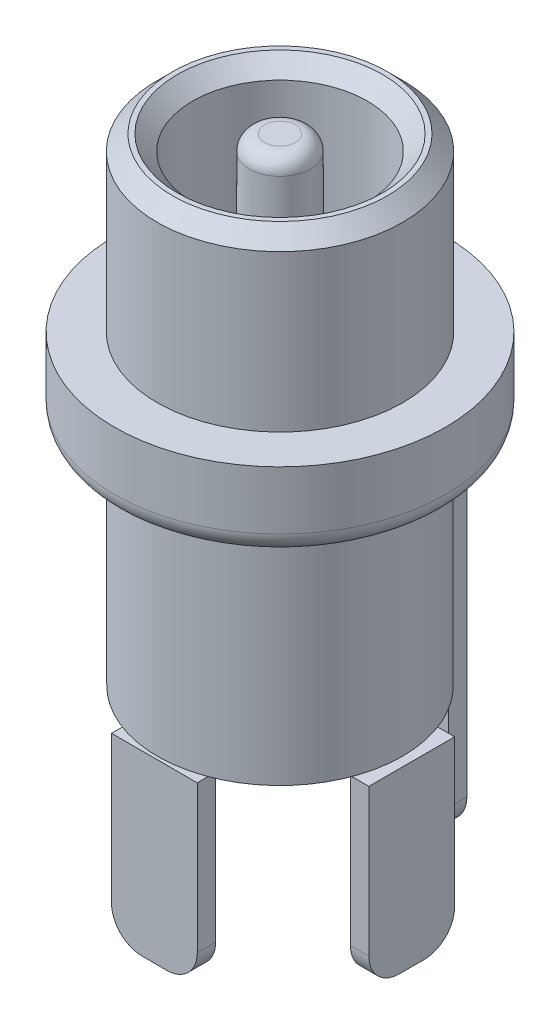
SolidWorks part; units mm, degrees
ref_plane "Front Plane" through (0, 0, 0) normal (0, 0, 1) x (1, 0, 0)
ref_plane "Top Plane" through (0, 0, 0) normal (0, 1, 0) x (1, 0, 0)
ref_plane "Right Plane" through (0, 0, 0) normal (1, 0, 0) x (0, 0, -1)
sketch "Sketch1" plane through (0, 0, 0) normal (0, 0, 1) x (1, 0, 0)
  line L0 (0, 0) -> (0, 15.6)
  line L1 (0, 15.6) -> (-4.01, 15.6)
  line L2 (-4.01, 15.6) -> (-4.01, 10)
  line L3 (-4.01, 10) -> (-5.4, 10)
  line L4 (-5.4, 10) -> (-5.4, 7.4)
  line L5 (-5.4, 7.4) -> (-4, 7.4)
  line L6 (-4, 7.4) -> (-4, 0)
  line L7 (-4, 0) -> (0, 0)
  line L8 (-4, 7.4) -> (0, 7.4)
  dimension "D1" = 5.6
  dimension "D2" = 10
  dimension "D3" = 2.6
  dimension "D4" = 4.01
  dimension "D5" = 5.4
  dimension "D6" = 4
revolve "Revolve1" add sketch "Sketch1" angle 360 about L0 region at (-2.2724, 11.2227, 0)
cosmetic thread "Cosmetic Thread2" parameters "D2"=8
fillet "Fillet1" radius 0.7 1 edges at (5.4, 7.4, 0)
revolve "Revolve2" add sketch "Sketch1<3>" angle 360 about L0 region at (-2, 3.7, 0)
sketch "Sketch1<3>" plane through (0, 0, 0) normal (0, 0, 1) x (1, 0, 0) same geometry as "Sketch1"
sketch "Sketch2" plane through (0, 15.6, 0) normal (0, 1, 0) x (1, 0, 0)
  circle A0 centre (0, 0) radius 1
  circle A1 centre (0, 0) radius 2.85
  dimension "D1" = 2
  dimension "D2" = 5.7
extrude "Cut-Extrude1" cut sketch "Sketch2" against normal blind 5.6
fillet "Fillet2" radius 0.5 1 edges at (-1, 15.6, 0)
chamfer "Chamfer1" distance 0.5 angle 45 2 edges at (4.01, 15.6, 0) (-2.85, 15.6, 0)
sketch "Sketch15" plane through (0, 0, 0) normal (0, -1, 0) x (1, 0, 0)
  line L0 (0, 3.8) -> (0, 0) construction
  line L1 (-1.4, 4.1) -> (1.4, 4.1)
  line L2 (-1.4, 4.1) -> (-1.4, 3.5)
  line L3 (-1.4, 3.5) -> (1.4, 3.5)
  line L4 (1.4, 4.1) -> (1.4, 3.5)
  line L5 (-1.4, 4.1) -> (1.4, 3.5) construction
  line L6 (-1.4, 3.5) -> (1.4, 4.1) construction
  line L7 (-1.4, -4.1) -> (1.4, -4.1)
  line L8 (-1.4, -4.1) -> (-1.4, -4.7)
  line L9 (-1.4, -4.7) -> (1.4, -4.7)
  line L10 (1.4, -4.1) -> (1.4, -4.7)
  line L11 (-1.4, -4.1) -> (1.4, -4.7) construction
  line L12 (-1.4, -4.7) -> (1.4, -4.1) construction
  line L13 (3.7, 1.4) -> (4.3, 1.4)
  line L14 (3.7, 1.4) -> (3.7, -1.4)
  line L15 (3.7, -1.4) -> (4.3, -1.4)
  line L16 (4.3, 1.4) -> (4.3, -1.4)
  line L17 (3.7, 1.4) -> (4.3, -1.4) construction
  line L18 (3.7, -1.4) -> (4.3, 1.4) construction
  line L19 (0, 0) -> (0, -4.4) construction
  line L20 (0, 0) -> (4, 0) construction
  point P0 (0, 3.8)
  point P5 (0, -4.4)
  point P10 (4, 0)
  dimension "D1" = 2.8
  dimension "D2" = 0.6
  dimension "D3" = 3.8
  dimension "D4" = 4.4
  dimension "D5" = 4
extrude "Boss-Extrude1" add sketch "Sketch15" along normal blind 5.8 separate body
extrude "Boss-Extrude2" add sketch "Sketch15<2>" against normal up to surface (7.4 mm away) contours L10 L7 L8 L9 region at (0, 0, -4.4) up to face at (-4.7, 7.4, 0)
sketch "Sketch15<2>" plane through (0, 0, 0) normal (0, -1, 0) x (1, 0, 0) same geometry as "Sketch15"
fillet "Fillet3" radius 1 2 edges at (-1.4, -5.8, 3.8) (1.4, -5.8, 3.8)
fillet "Fillet4" radius 1 2 edges at (-1.4, -5.8, -4.4) (1.4, -5.8, -4.4)
fillet "Fillet5" radius 1 2 edges at (4, -5.8, 1.4) (4, -5.8, -1.4)
sketch "Sketch16" plane through (0, 10, 0) normal (0, 1, 0) x (1, 0, 0)
  line L0 (-5.4, 0) -> (5.4, 0) construction
  line L1 (0, 5.4) -> (0, -5.4) construction
  circle A0 centre (0, 0) radius 5.4 construction
ref_axis "Axis1" through (-5.4, 10, 0) along (1, 0, 0)
ref_axis "Axis2" through (0, 10, -5.4) along (0, 0, 1)
